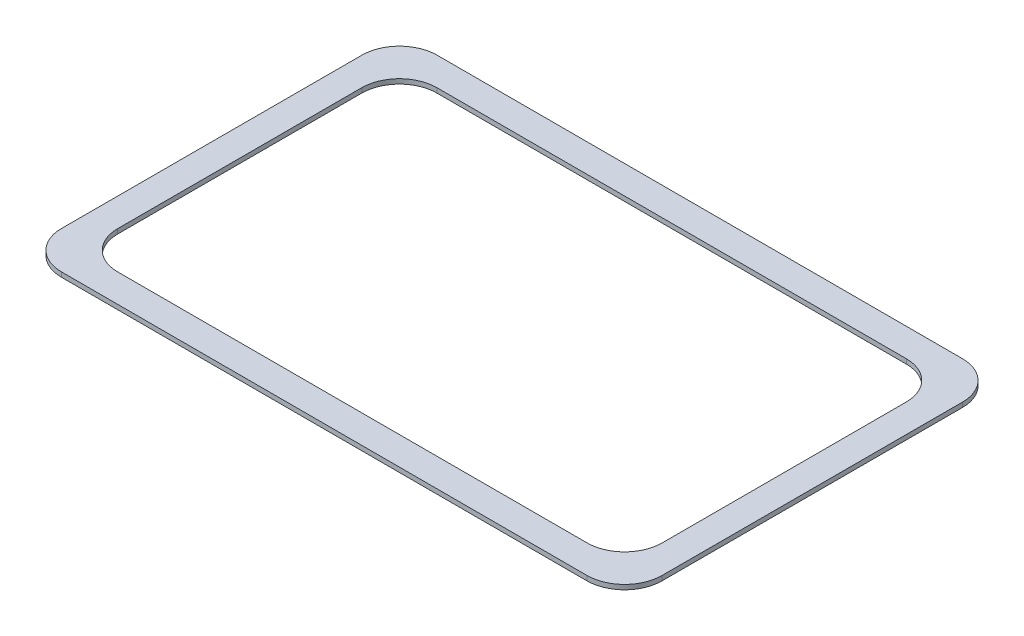
SolidWorks part; units mm, degrees
ref_plane "Front Plane" through (0, 0, 0) normal (0, 0, 1) x (1, 0, 0)
ref_plane "Top Plane" through (0, 0, 0) normal (0, 1, 0) x (1, 0, 0)
ref_plane "Right Plane" through (0, 0, 0) normal (1, 0, 0) x (0, 0, -1)
sketch "Sketch2" plane through (0, -26.8786, 0) normal (0, -1, 0) x (-1, 0, 0)
  line L13 (51.6556, 34.7934) -> (-151.5444, 34.7327) construction
  line L14 (-129.3194, -19.212) -> (29.4306, -19.212)
  line L15 (-142.0194, -6.512) -> (-142.0194, 76.038)
  line L16 (-129.3194, 88.738) -> (29.4306, 88.738)
  line L17 (42.1306, -6.512) -> (42.1306, 76.038)
  line L18 (-142.0194, -19.212) -> (42.1306, 88.738) construction
  line L19 (-142.0194, 88.738) -> (42.1306, -19.212) construction
  line L21 (-138.8634, 98.2364) -> (38.9366, 98.2896)
  line L22 (51.6404, 85.5934) -> (51.6708, -16.0066)
  line L23 (-138.8254, -28.7635) -> (38.9746, -28.7104)
  line L24 (-151.5596, 85.5327) -> (-151.5292, -16.0673)
  arc A12 (-129.3194, -19.212) -> (-142.0194, -6.512) centre (-129.3194, -6.512) cw
  arc A13 (29.4306, -19.212) -> (42.1306, -6.512) centre (29.4306, -6.512) ccw
  arc A14 (29.4306, 88.738) -> (42.1306, 76.038) centre (29.4306, 76.038) cw
  arc A15 (-142.0194, 76.038) -> (-129.3194, 88.738) centre (-129.3194, 76.038) cw
  arc A16 (-151.5292, -16.0673) -> (-138.8254, -28.7635) centre (-138.8292, -16.0635) ccw
  arc A17 (38.9746, -28.7104) -> (51.6708, -16.0066) centre (38.9708, -16.0104) ccw
  arc A18 (51.6404, 85.5934) -> (38.9366, 98.2896) centre (38.9404, 85.5896) ccw
  arc A19 (-138.8634, 98.2364) -> (-151.5596, 85.5327) centre (-138.8596, 85.5365) ccw
  point P0 (-49.9444, 34.763)
  dimension "D3" = 12.7
  dimension "D1" = 9.525
  dimension "D2" = 9.525
extrude "MainBody" add sketch "Sketch2" along normal blind 1.5875
equation "\"ClampDepth\"= 3 / 8in"
equation "\"D1@Sketch2\"=\"ClampDepth\""
equation "\"D2@Sketch2\"=\"ClampDepth\""
